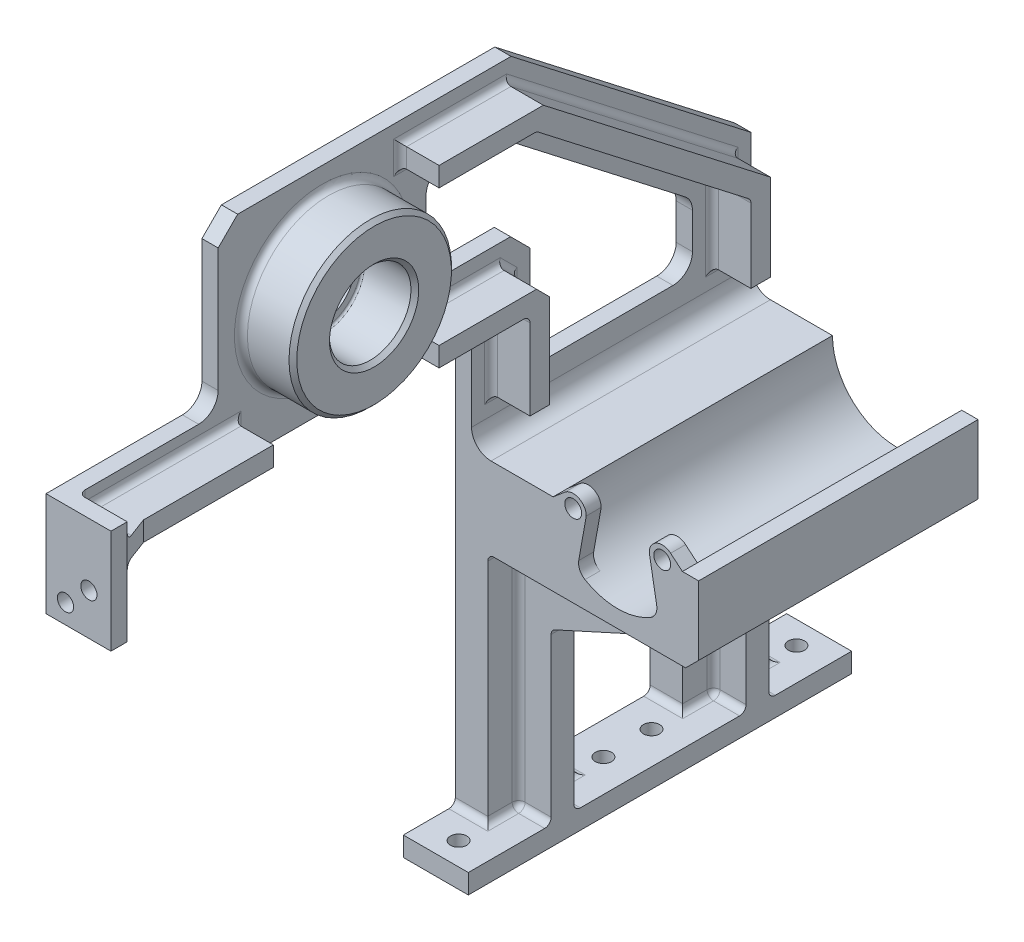
SolidWorks part; units mm, degrees
material "PLA2"
ref_plane "Front Plane" through (0, 0, 0) normal (0, 0, 1) x (1, 0, 0)
ref_plane "Top Plane" through (0, 0, 0) normal (0, 1, 0) x (1, 0, 0)
ref_plane "Right Plane" through (0, 0, 0) normal (1, 0, 0) x (0, 0, -1)
sketch "Profile-Sketch" plane through (0, 0, 0) normal (1, 0, 0) x (0, 0, -1)
  line L0 (0, 0) -> (50000, 0) construction
  line L1 (0, 0) -> (0, 50000) construction
  line L2 (0, 0) -> (0, 114.3) construction
  line L3 (0, 114.3) -> (63.5, 165.1) construction
  line L4 (63.5, 165.1) -> (190.5, 165.1) construction
  line L5 (50.8, 65.532) -> (50.8, 107.95) construction
  line L6 (35.814, 79.502) -> (65.786, 79.502) construction
  line L7 (35.814, 79.502) -> (35.814, 51.562) construction
  line L8 (35.814, 51.562) -> (65.786, 51.562) construction
  line L9 (65.786, 79.502) -> (65.786, 51.562) construction
  line L10 (35.814, 79.502) -> (65.786, 51.562) construction
  line L11 (35.814, 51.562) -> (65.786, 79.502) construction
  line L12 (35.814, 65.532) -> (65.786, 65.532) construction
  line L13 (65.786, 75.565) -> (75.692, 75.565) construction
  line L14 (75.692, 75.565) -> (75.692, 55.499) construction
  line L15 (65.786, 55.499) -> (75.692, 55.499) construction
  line L16 (75.692, 67.532) -> (80.772, 67.532) construction
  line L17 (80.772, 67.532) -> (80.772, 69.0245) construction
  line L18 (80.772, 69.0245) -> (83.312, 69.0245) construction
  line L19 (83.312, 69.0245) -> (83.312, 78.0288) construction
  line L20 (83.312, 78.0288) -> (130.302, 78.0288) construction
  line L21 (130.302, 78.0288) -> (130.302, 53.0352) construction
  line L22 (83.312, 53.0352) -> (130.302, 53.0352) construction
  line L23 (83.312, 62.0395) -> (83.312, 53.0352) construction
  line L24 (80.772, 62.0395) -> (83.312, 62.0395) construction
  line L25 (80.772, 63.532) -> (80.772, 62.0395) construction
  line L26 (75.692, 63.532) -> (80.772, 63.532) construction
  circle A0 centre (50.8, 107.95) radius 11.557 construction
  circle A1 centre (50.8, 107.95) radius 31.496 construction
  point P12 (50.8, 65.532)
  point P24 (75.692, 65.532)
  point P33 (130.302, 65.532)
  dimension "D1" = 23.114
  dimension "D8" = 62.992
  dimension "D9" = 27.94
  dimension "D2" = 107.95
  dimension "D3" = 114.3
  dimension "D4" = 50.8
  dimension "D5" = 63.5
  dimension "D6" = 50.8
  dimension "D7" = 127
  dimension "D10" = 29.972
  dimension "D11" = 20.066
  dimension "D12" = 9.906
  dimension "D13" = 42.418
  dimension "D14" = 5.08
  dimension "D15" = 2.54
  dimension "D16" = 4
  dimension "D17" = 6.985
  dimension "D18" = 24.9936
  dimension "D19" = 46.99
sketch "Sketch3" plane through (0, 0, 0) normal (1, 0, 0) x (0, 0, -1)
  line L10 (30.48, 128.27) -> (30.48, 86.36)
  line L11 (30.48, 86.36) -> (71.12, 86.36)
  line L12 (71.12, 86.36) -> (71.12, 128.27)
  line L13 (71.12, 128.27) -> (30.48, 128.27)
  line L14 (80.01, 73.66) -> (80.01, 49.53)
  line L15 (80.01, 49.53) -> (134.62, 49.53)
  line L16 (134.62, 49.53) -> (134.62, 73.66)
  line L17 (134.62, 73.66) -> (80.01, 73.66)
  circle A1 centre (50.8, 107.95) radius 6.35
  dimension "D9" = 12.7
  dimension "D1" = 20.32
  dimension "D2" = 20.32
  dimension "D3" = 20.32
  dimension "D4" = 21.59
  dimension "D5" = 54.61
  dimension "D6" = 29.21
  dimension "D7" = 34.29
  dimension "D8" = 58.42
extrude "Base-Plates" add sketch "Sketch3" along normal blind 3.175
sketch "Sketch6" plane through (3.175, 0, 0) normal (-1, 0, 0) x (0, 0, 1)
  circle A2 centre (-50.8, 107.95) radius 7.9629
  circle A3 centre (-50.8, 107.95) radius 15.875
  dimension "D1" = 15.9258
  dimension "D2" = 31.75
extrude "BearingHousing" add sketch "Sketch6" against normal blind 10.16
sketch "Sketch7" plane through (0, 0, -80.01) normal (0, 0, 1) x (1, 0, 0)
  line L2 (0, 78.0288) -> (0, 53.0352) construction
  line L3 (19.1135, 65.532) -> (44.3865, 65.532) construction
  line L8 (47.5615, 49.53) -> (47.5615, 65.532)
  line L9 (47.5615, 65.532) -> (44.3865, 65.532)
  line L10 (47.5615, 49.53) -> (3.175, 49.53)
  line L11 (3.175, 49.53) -> (3.175, 65.532)
  line L12 (3.175, 73.66) -> (3.175, 49.53) construction
  line L13 (3.175, 65.532) -> (19.1135, 65.532)
  arc A0 (19.1135, 65.532) -> (44.3865, 65.532) centre (31.75, 65.532) ccw
  point P0 (0, 107.95)
  dimension "D2" = 25.273
  dimension "D1" = 42.418
  dimension "D3" = 31.75
  dimension "D4" = 3.175
extrude "Motor-Mount" add sketch "Sketch7" against normal up to surface (54.61 mm away) up to face at (1.5875, 61.595, -134.62)
sketch "Sketch8" plane through (0, 0, -80.01) normal (0, 0, 1) x (1, 0, 0)
  line L0 (19.1135, 65.532) -> (44.3865, 65.532) construction
  line L1 (31.75, 59.182) -> (31.75, 50059.182) construction
  line L2 (19.1135, 65.532) -> (21.4118, 67.4727)
  line L11 (25.5905, 65.532) -> (23.8513, 55.6684)
  line L12 (23.8513, 55.6684) -> (19.1135, 55.6684)
  line L13 (19.1135, 55.6684) -> (19.1135, 65.532)
  line L14 (44.3865, 55.6684) -> (44.3865, 65.532)
  line L15 (39.6487, 55.6684) -> (44.3865, 55.6684)
  line L16 (37.9095, 65.532) -> (39.6487, 55.6684)
  line L17 (44.3865, 65.532) -> (42.0882, 67.4727)
  circle A0 centre (23.0505, 65.532) radius 1.651
  arc A1 (25.5905, 65.532) -> (21.4118, 67.4727) centre (23.0505, 65.532) ccw
  arc A4 (19.1135, 65.532) -> (44.3865, 65.532) centre (31.75, 65.532) ccw construction
  arc A5 (37.9095, 65.532) -> (42.0882, 67.4727) centre (40.4495, 65.532) cw
  circle A6 centre (40.4495, 65.532) radius 1.651
  point P2 (31.75, 65.532)
  dimension "D2" = 3.302
  dimension "D3" = 5.08
  dimension "D1" = 17.399
  dimension "D4" = 100
extrude "Motor-Mount-Holes" add sketch "Sketch8" against normal blind 2.921
sketch "Sketch9" plane through (0, 0, 0) normal (1, 0, 0) x (0, 0, -1)
  line L0 (71.12, 86.36) -> (80.01, 86.36)
  line L1 (80.01, 86.36) -> (80.01, 73.66)
  line L2 (71.12, 97.79) -> (91.44, 97.79)
  line L3 (71.12, 86.36) -> (71.12, 128.27) construction
  line L4 (91.44, 97.79) -> (91.44, 73.66)
  line L5 (134.62, 73.66) -> (80.01, 73.66) construction
  line L6 (91.44, 73.66) -> (80.01, 73.66)
  line L7 (71.12, 97.79) -> (71.12, 86.36)
  line L10 (134.62, 65.532) -> (134.62, 73.66) construction
  line L11 (134.62, 73.66) -> (123.19, 73.66)
  line L14 (71.12, 116.84) -> (71.12, 128.27)
  line L15 (71.12, 116.84) -> (83.82, 116.84)
  line L16 (83.82, 116.84) -> (123.19, 86.36)
  line L17 (123.19, 86.36) -> (123.19, 73.66)
  line L18 (71.12, 128.27) -> (87.7274, 128.27)
  line L19 (87.7274, 128.27) -> (134.62, 91.9661)
  line L20 (134.62, 91.9661) -> (134.62, 73.66)
  dimension "D1" = 11.43
  dimension "D2" = 11.43
  dimension "D3" = 11.43
  dimension "D4" = 11.43
  dimension "D5" = 11.43
  dimension "D6" = 12.7
  dimension "D7" = 12.7
extrude "Plate-Connection" add sketch "Sketch9" along normal up to surface (3.175 mm away) up to face at (3.175, 107.315, -50.8)
ref_plane "Legs-MidPlane" through (0, 0, -107.315) normal (0, 0, -1) x (-1, 0, 0)
sketch "Sketch12" plane through (0, 0, 0) normal (1, 0, 0) x (0, 0, -1)
  line L0 (80.01, 49.53) -> (96.52, 49.53)
  line L1 (134.62, 49.53) -> (80.01, 49.53) construction
  line L3 (-200000, 0) -> (250000, 0) construction
  line L4 (96.52, 0) -> (80.01, 0)
  line L5 (80.01, 0) -> (80.01, 49.53)
  line L6 (118.11, 49.53) -> (134.62, 49.53)
  line L7 (134.62, 49.53) -> (134.62, 0)
  line L8 (134.62, 0) -> (118.11, 0)
  line L12 (96.52, 49.53) -> (96.52, 0)
  line L13 (118.11, 49.53) -> (118.11, 0)
  dimension "D4" = 16.51
  dimension "D5" = 16.51
sketch "Sketch18" plane through (0, 0, 0) normal (1, 0, 0) x (0, 0, -1)
  line L0 (30.48, 96.52) -> (0, 96.52)
  line L1 (30.48, 128.27) -> (30.48, 86.36) construction
  line L2 (0, -200000) -> (0, 250000) construction
  line L3 (0, 96.52) -> (0, 86.36)
  line L4 (0, 86.36) -> (30.48, 86.36)
  line L5 (30.48, 86.36) -> (30.48, 96.52)
  line L6 (30.48, 86.36) -> (80.01, 86.36) construction
  dimension "D1" = 10.16
extrude "Bottom-Legs" add sketch "Sketch12" along normal blind 6.35
sketch "Sketch19" plane through (0, 0, 0) normal (0, -1, 0) x (1, 0, 0)
  line L0 (0, -69.85) -> (12.7, -69.85)
  line L1 (0, -30.48) -> (0, -80.01) construction
  line L2 (12.7, -69.85) -> (12.7, -144.78)
  line L3 (12.7, -144.78) -> (0, -144.78)
  line L4 (0, -144.78) -> (0, -69.85)
  line L5 (3.175, -80.01) -> (0, -80.01) construction
  line L6 (6.35, -134.62) -> (0, -134.62) construction
  dimension "D1" = 12.7
  dimension "D2" = 10.16
  dimension "D3" = 10.16
extrude "Bottom-Mount-Plate" add sketch "Sketch19" against normal blind 3.81
ref_plane "Single-Leg-MidPlane" through (0, 0, -88.265) normal (0, 0, 1) x (1, 0, 0)
sketch "Sketch20" plane through (0, 0, -88.265) normal (0, 0, 1) x (1, 0, 0)
  line L0 (40.64, 49.53) -> (12.7, 36.83)
  line L1 (47.5615, 49.53) -> (6.35, 49.53) construction
  line L2 (12.7, 36.83) -> (12.7, 6.985)
  line L3 (12.7, 6.985) -> (12.7, 3.81)
  line L4 (12.7, 3.81) -> (6.35, 3.81)
  line L5 (12.7, 3.81) -> (0, 3.81) construction
  line L6 (6.35, 3.81) -> (6.35, 49.53)
  line L7 (6.35, 49.53) -> (40.64, 49.53)
  line L8 (0, 86.36) -> (0, 3.81) construction
  dimension "D1" = 12.7
  dimension "D2" = 3.175
  dimension "D3" = 12.7
  dimension "D4" = 40.64
extrude "Leg-Stiffener" add sketch "Sketch20" along normal mid plane 4.445
mirror "Mirror1" about plane through (0, 0, -107.315) normal (0, 0, -1) of "Leg-Stiffener"
sketch "Sketch21" plane through (0, 0, 0) normal (0, -1, 0) x (1, 0, 0)
  line L0 (6.35, -134.62) -> (6.35, -128.5875) construction
  line L1 (6.35, -128.5875) -> (12.7, -128.5875) construction
  line L2 (12.7, -128.5875) -> (12.7, -144.78) construction
  line L3 (12.7, -144.78) -> (0, -144.78) construction
  line L4 (12.7, -69.85) -> (0, -69.85)
  line L5 (0, -69.85) -> (0, -144.78)
  line L6 (0, -144.78) -> (12.7, -144.78)
  line L7 (12.7, -144.78) -> (12.7, -69.85)
  line L8 (12.7, -69.85) -> (0, -69.85) construction
  line L9 (0, -69.85) -> (0, -144.78) construction
  line L10 (0, -144.78) -> (12.7, -144.78) construction
  line L11 (12.7, -144.78) -> (12.7, -69.85) construction
  line L12 (0, -144.78) -> (0, -134.62) construction
  line L13 (0, -134.62) -> (6.35, -134.62) construction
  line L14 (12.7, -69.85) -> (12.7, -86.0425) construction
  line L15 (12.7, -86.0425) -> (6.35, -86.0425) construction
  line L16 (6.35, -86.0425) -> (6.35, -80.01) construction
  line L17 (6.35, -80.01) -> (0, -80.01) construction
  line L18 (0, -80.01) -> (0, -69.85) construction
  line L19 (0, -69.85) -> (12.7, -69.85) construction
  line L20 (12.7, -124.1425) -> (6.35, -124.1425) construction
  line L21 (6.35, -124.1425) -> (6.35, -118.11) construction
  line L22 (6.35, -118.11) -> (0, -118.11) construction
  line L23 (0, -118.11) -> (0, -96.52) construction
  line L24 (0, -96.52) -> (6.35, -96.52) construction
  line L25 (6.35, -96.52) -> (6.35, -90.4875) construction
  line L26 (6.35, -90.4875) -> (12.7, -90.4875) construction
  line L27 (12.7, -90.4875) -> (12.7, -124.1425) construction
  line L28 (6.35, -134.62) -> (6.35, -128.5875) construction
  line L29 (6.35, -128.5875) -> (12.7, -128.5875) construction
  line L30 (12.7, -128.5875) -> (12.7, -144.78) construction
  line L31 (12.7, -144.78) -> (0, -144.78) construction
  line L32 (0, -144.78) -> (0, -134.62) construction
  line L33 (0, -134.62) -> (6.35, -134.62) construction
  line L34 (12.7, -69.85) -> (12.7, -86.0425) construction
  line L35 (12.7, -86.0425) -> (6.35, -86.0425) construction
  line L36 (6.35, -86.0425) -> (6.35, -80.01) construction
  line L37 (6.35, -80.01) -> (0, -80.01) construction
  line L38 (0, -80.01) -> (0, -69.85) construction
  line L39 (0, -69.85) -> (12.7, -69.85) construction
  line L40 (12.7, -124.1425) -> (6.35, -124.1425) construction
  line L41 (6.35, -124.1425) -> (6.35, -118.11) construction
  line L42 (6.35, -118.11) -> (0, -118.11) construction
  line L43 (0, -118.11) -> (0, -96.52) construction
  line L44 (0, -96.52) -> (6.35, -96.52) construction
  line L45 (6.35, -96.52) -> (6.35, -90.4875) construction
  line L46 (6.35, -90.4875) -> (12.7, -90.4875) construction
  line L47 (12.7, -90.4875) -> (12.7, -124.1425) construction
  line L48 (0, -107.315) -> (47.5615, -107.315) construction
  line L49 (47.5615, -134.62) -> (47.5615, -80.01) construction
  circle A0 centre (6.35, -74.295) radius 1.5875
  circle A1 centre (6.35, -102.616) radius 1.5875
  circle A2 centre (6.35, -140.335) radius 1.5875
  circle A3 centre (6.35, -112.014) radius 1.5875
  dimension "D2" = 3.175
  dimension "D7" = 3.175
  dimension "D3" = 6.35
  dimension "D4" = 33.02
  dimension "D5" = 4.699
  dimension "D6" = 6.35
  dimension "D8" = 74.295
  dimension "D9" = 102.616
  dimension "D10" = 112.014
  dimension "D11" = 140.335
extrude "Bottom-Mount-Holes" cut sketch "Sketch21" against normal up to surface (3.81 mm away) up to face at (6.35, 3.81, -107.315)
extrude "Side-Arm" add sketch "Sketch18" along normal up to surface (3.175 mm away) up to face at (3.175, 94.7057, -93.6171)
sketch "Sketch22" plane through (0, 0, 0) normal (0, 0, 1) x (1, 0, 0)
  line L0 (0, 96.52) -> (12.7, 96.52)
  line L1 (12.7, 96.52) -> (12.7, 76.2)
  line L2 (12.7, 76.2) -> (0, 76.2)
  line L3 (0, 86.36) -> (0, 3.81) construction
  line L4 (0, 76.2) -> (0, 96.52)
  line L5 (3.175, 86.36) -> (0, 86.36) construction
  dimension "D1" = 12.7
  dimension "D2" = 10.16
extrude "Side-Arm-Plate" add sketch "Sketch22" against normal blind 3.175
ref_plane "Arm-MidPlane" through (0, 91.44, 0) normal (0, 1, 0) x (1, 0, 0)
sketch "Sketch23" plane through (0, 91.44, 0) normal (0, 1, 0) x (1, 0, 0)
  line L0 (3.175, 33.655) -> (10.795, 33.655)
  line L1 (3.175, 87.7274) -> (3.175, 30.48) construction
  line L2 (10.795, 33.655) -> (10.795, 8.255)
  line L3 (10.795, 8.255) -> (12.7, 3.175)
  line L4 (3.175, 33.655) -> (3.175, 3.175)
  line L5 (3.175, 3.175) -> (12.7, 3.175)
  line L6 (0, 30.48) -> (0, 0) construction
  line L7 (3.175, 34.925) -> (13.335, 34.925) construction
  dimension "D1" = 10.795
  dimension "D2" = 5.08
  dimension "D3" = 1.27
extrude "Arm-Stiffener" add sketch "Sketch23" along normal mid plane 3.81
sketch "Sketch24" plane through (0, 0, -3.175) normal (0, 0, -1) x (-1, 0, 0)
  line L1 (0, 3.81) -> (0, 91.9661) construction
  line L2 (0, 91.9661) -> (0, 128.27) construction
  line L3 (0, 76.2) -> (-12.7, 76.2) construction
  circle A0 centre (-8.382, 84.328) radius 1.5875
  circle A1 centre (-3.81, 80.01) radius 1.5875
  dimension "D1" = 3.175
  dimension "D2" = 3.175
  dimension "D3" = 8.382
  dimension "D4" = 3.81
  dimension "D5" = 8.128
  dimension "D6" = 3.81
  dimension "D7" = 84.328
  dimension "D8" = 80.01
extrude "Side-Mount-Holes" cut sketch "Sketch24" against normal up to surface (3.175 mm away) up to face at (6.35, 86.36, 0)
fillet "Fillet1" radius 1.27 24 edges at (40.64, 49.53, -126.365) (40.64, 49.53, -88.265) (23.495, 49.53, -124.1425) (23.495, 49.53, -128.5875) (6.35, 49.53, -131.6037) (6.35, 49.53, -83.0262) (12.7, 36.83, -126.365) (6.35, 26.67, -124.1425) (6.35, 26.67, -128.5875) (6.35, 3.81, -131.6038) (6.35, 3.81, -83.0262) (23.495, 49.53, -90.4875) (23.495, 49.53, -86.0425) (12.7, 36.83, -88.265) (6.35, 26.67, -86.0425) (6.35, 26.67, -90.4875) (9.525, 3.81, -90.4875) (9.525, 3.81, -86.0425) (3.175, 3.81, -134.62) (3.175, 3.81, -118.11) (3.175, 3.81, -96.52) (3.175, 3.81, -80.01) (9.525, 3.81, -128.5875) (9.525, 3.81, -124.1425)
fillet "Fillet2" radius 3.81 11 edges at (1.5875, 96.52, -30.48) (1.5875, 86.36, -80.01) (3.175, 65.532, -107.315) (1.5875, 86.36, -123.19) (1.5875, 116.84, -83.82) (1.5875, 116.84, -71.12) (1.5875, 97.79, -71.12) (1.5875, 73.66, -91.44) (1.5875, 73.66, -123.19) (3.81, 49.53, -96.52) (3.81, 49.53, -118.11)
fillet "Fillet3" radius 1.27 8 edges at (1.5875, 86.36, -3.175) (3.175, 87.9475, -3.175) (3.175, 89.535, -18.415) (7.9375, 89.535, -3.175) (3.175, 93.345, -18.415) (3.175, 94.9325, -3.175) (7.9375, 93.345, -3.175) (3.175, 91.44, -33.655)
chamfer "Chamfer1" distance 3.81 angle 45 2 edges at (1.5875, 128.27, -30.48) (1.5875, 97.79, -91.44)
fillet "Fillet4" radius 2.54 2 edges at (23.8513, 55.6684, -81.4705) (39.6487, 55.6684, -81.4705)
chamfer "Chamfer2" distance 0.762 angle 45 2 edges at (13.335, 107.95, -42.8371) (13.335, 107.95, -34.925)
sketch "Sketch25" plane through (3.175, 0, 0) normal (1, 0, 0) x (0, 0, -1)
  line L0 (68.2212, 122.555) -> (85.7737, 122.555) construction
  line L1 (85.7737, 122.555) -> (128.905, 89.163) construction
  line L2 (128.905, 89.163) -> (128.905, 72.2985) construction
  line L3 (84.8499, 116.0427) -> (121.7124, 87.504) construction
  line L4 (94.6916, 108.4233) -> (101.6887, 117.4613) construction
  line L5 (134.62, 91.9661) -> (87.7274, 128.27) construction
  line L6 (123.19, 81.9861) -> (134.62, 81.9861) construction
  line L7 (123.19, 84.4913) -> (123.19, 77.47) construction
  line L8 (134.62, 69.342) -> (134.62, 91.9661) construction
  line L9 (77.1343, 97.79) -> (77.1343, 86.36) construction
  line L10 (87.63, 97.79) -> (74.93, 97.79) construction
  line L11 (4.445, 86.36) -> (76.2, 86.36) construction
  line L12 (80.01, 82.6135) -> (91.44, 82.6135) construction
  line L13 (80.01, 82.55) -> (80.01, 69.342) construction
  line L14 (91.44, 77.47) -> (91.44, 93.98) construction
  line L15 (80.2651, 128.27) -> (80.2651, 116.84) construction
  line L16 (87.7274, 128.27) -> (34.29, 128.27) construction
  line L17 (74.93, 116.84) -> (82.5175, 116.84) construction
  line L18 (66.04, 124.46) -> (66.04, 120.65)
  line L19 (66.04, 120.65) -> (85.1225, 120.65)
  line L20 (85.1225, 120.65) -> (127, 88.2287)
  line L21 (127, 88.2287) -> (127, 73.152)
  line L22 (127, 73.152) -> (130.81, 73.152)
  line L23 (130.81, 73.152) -> (130.81, 90.0974)
  line L24 (130.81, 90.0974) -> (86.425, 124.46)
  line L25 (86.425, 124.46) -> (66.04, 124.46)
  line L26 (108.6175, 107.2787) -> (106.2851, 104.266) construction
  line L27 (127, 78.9541) -> (130.81, 78.9541) construction
  line L28 (134.62, 65.532) -> (82.931, 65.532) construction
  line L29 (66.04, 92.075) -> (85.725, 92.075) construction
  line L30 (85.725, 92.075) -> (85.725, 73.152) construction
  line L31 (66.04, 93.98) -> (87.63, 93.98)
  line L32 (87.63, 93.98) -> (87.63, 73.152)
  line L33 (87.63, 73.152) -> (83.82, 73.152)
  line L34 (83.82, 73.152) -> (83.82, 90.17)
  line L35 (83.82, 90.17) -> (66.04, 90.17)
  line L36 (66.04, 90.17) -> (66.04, 93.98)
  circle A0 centre (50.8, 107.95) radius 6.35 construction
  point P10 (98.1902, 112.9423)
  point P29 (77.1343, 92.075)
  point P30 (85.725, 82.6135)
  point P31 (128.905, 81.9861)
  point P32 (80.2651, 122.555)
  point P47 (107.4513, 105.7724)
  point P48 (66.04, 122.555)
  point P49 (128.905, 78.9541)
  dimension "D1" = 3.81
  dimension "D2" = 3.81
  dimension "D3" = 3.81
  dimension "D4" = 15.24
  dimension "D5" = 7.62
  dimension "D6" = 3.81
  dimension "D7" = 3.81
  dimension "D8" = 7.62
  dimension "D9" = 15.24
extrude "Mid-Stiffeners" add sketch "Sketch25" along normal blind 7.62
chamfer "Chamfer3" distance 2.54 angle 45 1 edges at (6.985, 93.98, -87.63)
fillet "Fillet6" radius 1.27 18 edges at (3.175, 124.46, -76.2325) (3.175, 122.555, -66.04) (6.985, 120.65, -85.1225) (3.175, 120.65, -75.5812) (3.175, 107.2787, -108.6175) (3.175, 81.6247, -130.81) (3.175, 73.152, -128.905) (3.175, 104.4393, -106.0612) (6.985, 88.2287, -127) (3.175, 80.6903, -127) (3.175, 73.152, -85.725) (3.175, 92.075, -66.04) (3.175, 93.98, -75.565) (3.175, 92.71, -86.36) (3.175, 82.296, -87.63) (3.175, 81.661, -83.82) (6.985, 90.17, -83.82) (3.175, 90.17, -74.93)
chamfer "Chamfer4" distance 2.54 angle 45 1 edges at (47.5615, 49.53, -107.315)
fillet "Fillet7" radius 1.27 1 edges at (3.175, 107.95, -34.925)
fillet "Fillet8" radius 0.381 1 edges at (3.175, 107.95, -58.7629)
ref_plane "Plane1" through (8.255, 0, 0) normal (1, 0, 0) x (0, 0, -1)
sketch "Sketch26" plane through (8.255, 0, 0) normal (1, 0, 0) x (0, 0, -1)
  circle A1 centre (50.8, 107.95) radius 7.5819
  circle A2 centre (50.8, 107.95) radius 7.5819 construction
  point P1 (50.8, 107.95)
  dimension "D1" = 0
equation "\"D2@Sketch9\"=\"D1@Sketch9\""
equation "\"D3@Sketch9\"=\"D1@Sketch9\""
equation "\"D4@Sketch9\"=\"D1@Sketch9\""
equation "\"D5@Sketch9\"=\"D1@Sketch9\""
equation "\"D5@Sketch12\"=\"D4@Sketch12\""
equation "\"D7@Sketch21\"=\"D2@Sketch21\""
equation "\"D2@Sketch25\"=\"D1@Sketch25\""
equation "\"D3@Sketch25\"=\"D1@Sketch25\""
equation "\"D7@Sketch25\"=\"D1@Sketch25\""
equation "\"D6@Sketch25\"=\"D1@Sketch25\""
